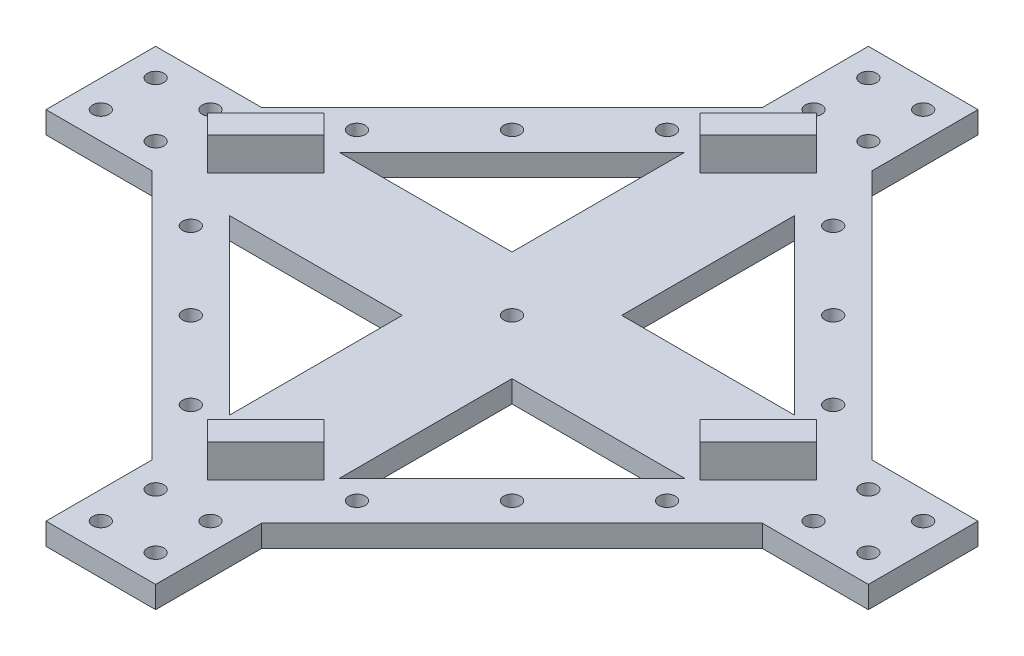
SolidWorks part; units mm, degrees
ref_plane "Front Plane" through (0, 0, 0) normal (0, 0, 1) x (1, 0, 0)
ref_plane "Top Plane" through (0, 0, 0) normal (0, 1, 0) x (1, 0, 0)
ref_plane "Right Plane" through (0, 0, 0) normal (1, 0, 0) x (0, 0, -1)
sketch "Sketch1" plane through (0, 0, 0) normal (0, 1, 0) x (1, 0, 0)
  line L0 (20, 85) -> (85, 85)
  line L1 (0, 0) -> (20, 0)
  line L2 (0, 0) -> (0, 65)
  line L3 (0, 150) -> (20, 150)
  line L4 (20, 0) -> (20, 65)
  line L5 (-65, 85) -> (0, 85)
  line L6 (-65, 85) -> (-65, 65)
  line L7 (-65, 65) -> (0, 65)
  line L8 (85, 85) -> (85, 65)
  line L9 (0, 85) -> (0, 150)
  line L10 (20, 65) -> (85, 65)
  line L11 (20, 85) -> (20, 150)
  line L12 (-40, 85) -> (0, 125) construction
  line L13 (20, 125) -> (60, 85) construction
  line L14 (60, 65) -> (20, 25) construction
  line L15 (0, 25) -> (-40, 65) construction
  line L16 (0, 33.4853) -> (-31.5147, 65)
  line L17 (51.5147, 65) -> (20, 33.4853)
  line L18 (20, 116.5147) -> (51.5147, 85)
  line L19 (-31.5147, 85) -> (0, 116.5147)
  line L20 (0, 19.3431) -> (-45.6569, 65)
  line L21 (65.6569, 65) -> (20, 19.3431)
  line L22 (20, 130.6569) -> (65.6569, 85)
  line L23 (-45.6569, 85) -> (0, 130.6569)
  line L24 (-2.8284, 22.1716) -> (-42.8284, 62.1716) construction
  line L25 (-35.7574, 80.7574) -> (4.2426, 120.7574) construction
  line L26 (15.7574, 120.7574) -> (55.7574, 80.7574) construction
  line L27 (55.7574, 69.2426) -> (15.7574, 29.2426) construction
  line L28 (4.2426, 29.2426) -> (-35.7574, 69.2426) construction
  line L29 (62.8284, 62.1716) -> (22.8284, 22.1716) construction
  line L30 (22.8284, 127.8284) -> (62.8284, 87.8284) construction
  line L31 (-42.8284, 87.8284) -> (-2.8284, 127.8284) construction
  circle A0 centre (10, 75) radius 1.5
  point P9 (-65, 75)
  point P15 (10, 0)
  point P24 (10, 150)
  point P25 (85, 75)
  dimension "D13" = 3
  dimension "D1" = 20
  dimension "D2" = 150
  dimension "D3" = 150
  dimension "D4" = 20
  dimension "D5" = 75
  dimension "D6" = 75
  dimension "D7" = 25
  dimension "D8" = 25
  dimension "D9" = 25
  dimension "D10" = 25
  dimension "D11" = 6
  dimension "D12" = 4
extrude "Base" add sketch "Sketch1" along normal blind 4 contours L0 L11 L3 L9 L5 L6 L7 L2 L1 L4 L10 L8 | L23 L5 L19 L9 | L22 L11 L18 L0 | L20 L2 L16 L7 | L21 L10 L17 L4 region at (35.7574, 0, -82.8787) region at (39.5089, 0, -104.5089) region at (39.5089, 0, -45.4911) region at (-19.5089, 0, -104.5089) region at (-19.5089, 0, -45.4911)
sketch "Sketch2" plane through (0, 4, 0) normal (0, 1, 0) x (1, 0, 0)
  line L0 (40.5824, 150.4836) -> (-65.4836, 44.4176) construction
  line L1 (-65.4836, 44.4176) -> (-20.5824, -0.4836) construction
  line L2 (-20.5824, -0.4836) -> (85.4836, 105.5824) construction
  line L3 (85.4836, 105.5824) -> (40.5824, 150.4836) construction
  line L4 (15.3033, 35.402) -> (4.6967, 24.7954)
  line L5 (-22.7601, 42.2399) -> (42.1744, 107.1744) construction
  line L6 (4.6967, 24.7954) -> (8.2322, 21.2599)
  line L7 (20, 130.6569) -> (65.6569, 85) construction
  line L8 (0, 19.3431) -> (-45.6569, 65) construction
  line L9 (43.9142, 41.0858) -> (-21.0858, 106.0858) construction
  line L10 (8.2322, 21.2599) -> (18.8388, 31.8665)
  line L11 (18.8388, 31.8665) -> (15.3033, 35.402)
  line L12 (11.7678, 128.7401) -> (1.1612, 118.1335)
  line L13 (51.5147, 65) -> (20, 33.4853) construction
  line L14 (49.598, 69.6967) -> (60.2046, 80.3033)
  line L15 (60.2046, 80.3033) -> (63.7401, 76.7678)
  line L16 (63.7401, 76.7678) -> (53.1335, 66.1612)
  line L17 (53.1335, 66.1612) -> (49.598, 69.6967)
  line L18 (15.3033, 125.2046) -> (11.7678, 128.7401)
  line L19 (4.6967, 114.598) -> (15.3033, 125.2046)
  line L20 (1.1612, 118.1335) -> (4.6967, 114.598)
  line L21 (-43.7401, 73.2322) -> (-33.1335, 83.8388)
  line L22 (-40.2046, 69.6967) -> (-43.7401, 73.2322)
  line L23 (-29.598, 80.3033) -> (-40.2046, 69.6967)
  line L24 (-33.1335, 83.8388) -> (-29.598, 80.3033)
  point P7 (42.8284, 107.8284)
  point P11 (-22.8284, 42.1716)
  point P12 (63.033, 128.033)
  point P16 (35.7574, 49.2426)
  point P17 (-12.4506, 97.4506)
  point P20 (32.4506, 52.5494)
  point P22 (10, 30.0987)
  point P26 (54.9013, 75)
  point P27 (10, 75)
  dimension "D1" = 150
  dimension "D2" = 63.5
  dimension "D3" = 15
  dimension "D4" = 5
extrude "BatteryClip" add sketch "Sketch2" along normal blind 6
ref_axis "RotationalAxis" through (10, 4, -75) along (0, -1, 0)
hole_wizard "Ø3.0mm Dowel Hole2" positions "3DSketch2" profile "Sketch5" hole size "Ø3.0" standard "ANSI Metric" end condition through all
sketch3d "3DSketch2"
  line L1 (10, 4, 0) -> (10, 4, -50000) construction
  line L2 (0, 4, 0) -> (20, 4, 0) construction
  line L3 (0, 4, -150) -> (20, 4, -150) construction
  line L4 (-65, 4, -75) -> (49935, 4, -75) construction
  line L5 (-65, 4, -85) -> (-65, 4, -65) construction
  line L6 (85, 4, -85) -> (85, 4, -65) construction
  line L7 (0, 4, -65) -> (34230.8373, 4, -34295.8373) construction
  line L11 (-5.1508, 4, -31.565) -> (-33.435, 4, -59.8492) construction
  line L13 (0, 4, -33.4853) -> (-31.5147, 4, -65) construction
  point P0 (5, 4, -5)
  point P2 (5, 4, -15)
  point P4 (15, 4, -15)
  point P6 (15, 4, -5)
  point P17 (10, 4, 0)
  point P20 (10, 4, -150)
  point P27 (-65, 4, -75)
  point P30 (85, 4, -75)
  point P44 (-5.1508, 4, -31.565)
  point P46 (-19.2929, 4, -45.7071)
  point P48 (-33.435, 4, -59.8492)
  point P71 (0, 0, 0)
  dimension "D1" = 5
  dimension "D6" = 40
  dimension "D2" = 10
  dimension "D3" = 10
  dimension "D4" = 5
  dimension "D5" = 5
sketch "Sketch5" plane through (5, 4, -5) normal (1, 0, 0) x (0, 0, 1)
  line L0 (0, 0) -> (0, 4)
  line L1 (0, 4) -> (1.5, 4)
  line L2 (1.5, 4) -> (1.5, 0)
  line L5 (1.5, 0) -> (0, 0)
  line L11 (0, -6.35) -> (0, 107.95) construction
  dimension "Thru Hole Dia." = 3
  dimension "Thru Hole Depth" = 4
pattern_circular "CirPattern2" count 4 over 360 about axis through (10, 4, -75) along (0, -1, 0) of "Ø3.0mm Dowel Hole2"
ref_plane "Plane3" through (42.5, 0, -42.5) normal (-0.7071, 0, 0.7071) x (0.7071, 0, 0.7071)
